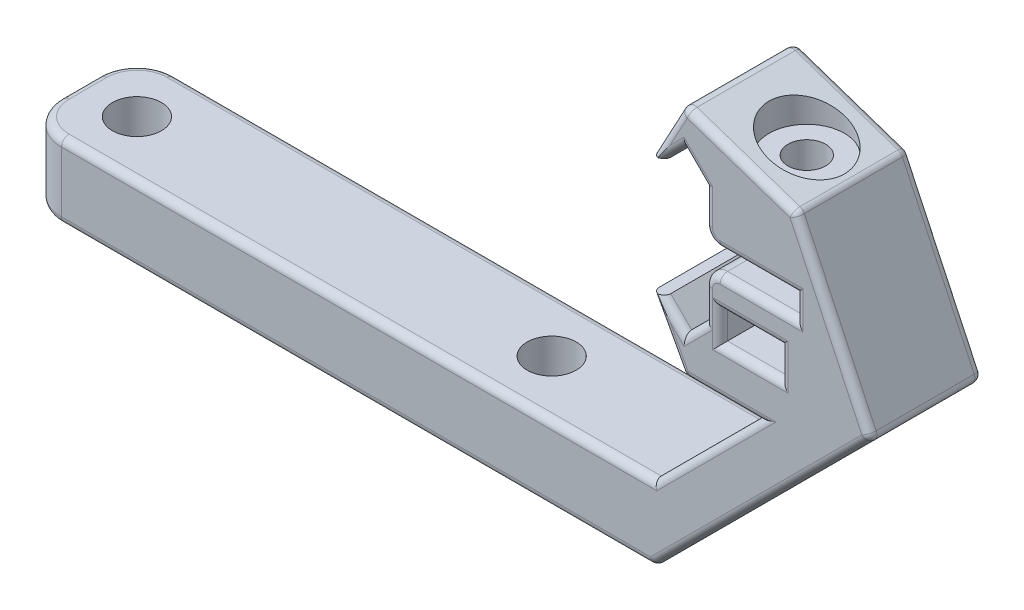
SolidWorks part; units mm, degrees
ref_plane "Front Plane" through (0, 0, 0) normal (0, 0, 1) x (1, 0, 0)
ref_plane "Top Plane" through (0, 0, 0) normal (0, 1, 0) x (1, 0, 0)
ref_plane "Right Plane" through (0, 0, 0) normal (1, 0, 0) x (0, 0, -1)
sketch "Sketch1" plane through (0, 0, 0) normal (0, 0, 1) x (1, 0, 0)
  line L0 (48.5324, 5) -> (67.3324, 23.8)
  line L1 (0, -5) -> (48.5324, -5)
  line L2 (0, -5) -> (0, 5)
  line L3 (0, 5) -> (48.5324, 5)
  line L4 (48.5324, -5) -> (48.5324, 5)
  line L5 (0, -5) -> (48.5324, 5) construction
  line L6 (0, 5) -> (48.5324, -5) construction
  line L7 (48.5324, -5) -> (77.3324, 23.8)
  line L8 (67.3324, 23.8) -> (77.3324, 23.8)
  line L9 (55.3324, 42.23) -> (52.5624, 45)
  line L12 (77.3324, 23.8) -> (67.3324, 23.8)
  line L13 (67.3324, 45) -> (67.3324, 23.8)
  line L14 (67.3324, 45) -> (77.3324, 23.8)
  line L15 (55.3324, 45) -> (67.3324, 45) construction
  line L19 (67.3324, 23.8) -> (67.3324, 45)
  line L20 (52.5624, 45) -> (49.7924, 42.23)
  line L21 (55.3324, 45) -> (49.7924, 45) construction
  line L22 (49.7924, 45) -> (49.7924, 42.23) construction
  line L23 (55.3324, 26.57) -> (52.5624, 23.8)
  line L24 (52.5624, 23.8) -> (49.7924, 26.57)
  line L25 (55.3324, 23.8) -> (49.7924, 23.8) construction
  line L26 (49.7924, 26.57) -> (49.7924, 23.8) construction
  line L27 (55.3324, 45) -> (55.3324, 42.23)
  line L28 (55.3324, 42.23) -> (55.3324, 26.57)
  line L29 (55.3324, 26.57) -> (55.3324, 23.8) construction
  line L30 (49.7924, 26.57) -> (48.2924, 26.57)
  line L31 (48.2924, 42.23) -> (52.5, 50)
  line L32 (49.7924, 42.23) -> (48.2924, 42.23)
  line L33 (48.2924, 26.57) -> (52.5, 18.8)
  line L34 (55.3324, 34.4) -> (67.3324, 34.4) construction
  line L35 (55.3324, 32.9) -> (67.3324, 32.9)
  line L36 (55.3324, 35.9) -> (67.3324, 35.9)
  line L37 (52.5, 18.8) -> (52.5, 23.8) construction
  line L38 (52.5, 50) -> (52.5, 45) construction
  line L40 (52.5, 50) -> (67.3324, 45)
  line L41 (67.3324, 32.9) -> (67.3324, 23.8)
  line L42 (67.3324, 32.9) -> (67.3324, 23.8)
  line L43 (52.5, 18.8) -> (62.3324, 18.8)
  line L44 (57.3324, 32.9) -> (57.3324, 24.9) construction
  line L45 (57.3324, 24.9) -> (65.3324, 24.9)
  line L46 (65.3324, 24.9) -> (65.3324, 32.9) construction
  line L47 (57.3324, 24.9) -> (57.3324, 28.9)
  line L48 (57.3324, 28.9) -> (65.3324, 28.9)
  line L49 (65.3324, 28.9) -> (65.3324, 24.9)
  line L51 (-35, -5) -> (0, -5)
  line L52 (-35, -5) -> (-35, 5)
  line L53 (-35, 5) -> (0, 5)
  line L54 (0, -5) -> (0, 5)
  line L55 (-35, -5) -> (0, 5) construction
  line L56 (-35, 5) -> (0, -5) construction
  point P0 (24.2662, 0)
  point P5 (0, 0)
  point P11 (-17.5, 0)
  point P28 (52.5624, 45)
  point P30 (52.5624, 23.8)
  point P41 (61.3324, 24.9)
  dimension "D1" = 135
  dimension "D2" = 10
  dimension "D3" = 21.2
  dimension "D4" = 40
  dimension "D5" = 52.5
  dimension "D6" = 8
  dimension "D7" = 1.5
  dimension "D8" = 12
  dimension "D9" = 1.5
  dimension "D10" = 5.54
  dimension "D11" = 2.77
  dimension "D12" = 1.5
  dimension "D13" = 5
  dimension "D14" = 6
  dimension "D15" = 8
  dimension "D16" = 4
  dimension "D17" = 35
extrude "Boss-Extrude1" add sketch "Sketch1" along normal blind 7.5 and the other way blind 7.5 contours L1 L4 L3 L2 | L8 L0 L4 L7 | L14 L13 L19 L8 | L19 L35 L28 L23 L24 L30 L33 | L40 L31 L32 L20 L9 L28 L36 L13 | L53 L52 L51 L2 region at (24.2662, 0, 0) region at (60.6075, 11.7249, 0) region at (57.4162, 19.0369, 0) region at (-17.5, 0, 0) region at (70.6658, 30.8667, 0) region at (59.475, 42.3299, 0)
sketch "Sketch2" plane through (0, 35.9, 0) normal (0, -1, 0) x (1, 0, 0)
  line L0 (55.3324, 7.5) -> (55.3324, -7.5) construction
  line L1 (55.3324, 7.5) -> (67.3324, 7.5) construction
  circle A0 centre (61.3324, 0) radius 2.5
  point P4 (55.3324, 0)
  dimension "D1" = 5
  dimension "D2" = 6
  dimension "D3" = 7.5
extrude "Cut-Extrude1" cut sketch "Sketch2" against normal through all
extrude "Cut-Extrude2" cut sketch "Sketch2<2>" along normal blind 16
sketch "Sketch2<2>" plane through (0, 35.9, 0) normal (0, -1, 0) x (1, 0, 0) same geometry as "Sketch2"
sketch "Sketch4" plane through (0, 0, 0) normal (0, 1, 0) x (1, 0, 0)
  circle A0 centre (61.3324, 0) radius 2.5
  circle A1 centre (61.3324, 0) radius 5
  dimension "D1" = 5
  dimension "D2" = 10
extrude "Cut-Extrude3" cut sketch "Sketch4" against normal blind 5 from offset 50
sketch "Sketch5" plane through (0, -5, 0) normal (0, -1, 0) x (1, 0, 0)
  line L0 (0, 0) -> (0, 7.5) construction
  line L1 (-35, 7.5) -> (48.5324, 7.5) construction
  circle A0 centre (27.5, 0) radius 3.25
  circle A1 centre (-27.5, 0) radius 3.25
  dimension "D2" = 6.5
  dimension "D1" = 55
  dimension "D3" = 27.5
  dimension "D4" = 7.5
extrude "Cut-Extrude4" cut sketch "Sketch5" against normal through all
fillet "Fillet1" radius 5 2 edges at (-35, 0, -7.5) (-35, 0, 7.5)
fillet "Fillet3" radius 2 2 edges at (55.3324, 35.9, 0) (55.3324, 32.9, 0)
fillet "Fillet2" radius 1 59 edges at (-33.5355, 5, 6.0355) (-33.5355, 5, -6.0355) (-33.5355, -5, 6.0355) (-33.5355, -5, -6.0355) (57.3324, 26.9, 7.5) (61.3324, 24.9, 7.5) (65.3324, 26.9, 7.5) (61.3324, 28.9, 7.5) (55.4324, 11.9, 7.5) (57.4162, 18.8, 7.5) (50.3962, 22.685, 7.5) (51.1774, 25.185, 7.5) (53.9474, 25.185, 7.5) (55.3324, 28.735, 7.5) (62.3324, 32.9, 7.5) (67.3324, 34.4, 7.5) (62.3324, 35.9, 7.5) (55.3324, 40.065, 7.5) (53.9474, 43.615, 7.5) (51.1774, 43.615, 7.5) (50.3962, 46.115, 7.5) (59.9162, 47.5, 7.5) (72.3324, 34.4, 7.5) (62.9324, 9.4, 7.5) (9.2662, -5, 7.5) (9.2662, 5, 7.5) (65.3324, 26.9, -7.5) (61.3324, 24.9, -7.5) (57.3324, 26.9, -7.5) (61.3324, 28.9, -7.5) (62.9324, 9.4, -7.5) (72.3324, 34.4, -7.5) (59.9162, 47.5, -7.5) (50.3962, 46.115, -7.5) (51.1774, 43.615, -7.5) (53.9474, 43.615, -7.5) (55.3324, 40.065, -7.5) (62.3324, 35.9, -7.5) (67.3324, 34.4, -7.5) (62.3324, 32.9, -7.5) (55.3324, 28.735, -7.5) (53.9474, 25.185, -7.5) (51.1774, 25.185, -7.5) (50.3962, 22.685, -7.5) (57.4162, 18.8, -7.5) (55.4324, 11.9, -7.5) (9.2662, 5, -7.5) (9.2662, -5, -7.5) (52.5, 18.8, 0) (52.5, 50, 0) (67.3324, 45, 0) (77.3324, 23.8, 0) (48.5324, -5, 0) (55.9182, 32.3142, 7.5) (55.9182, 36.4858, 7.5) (55.9182, 32.3142, -7.5) (55.9182, 36.4858, -7.5) (-35, 5, 0) (-35, -5, 0)
